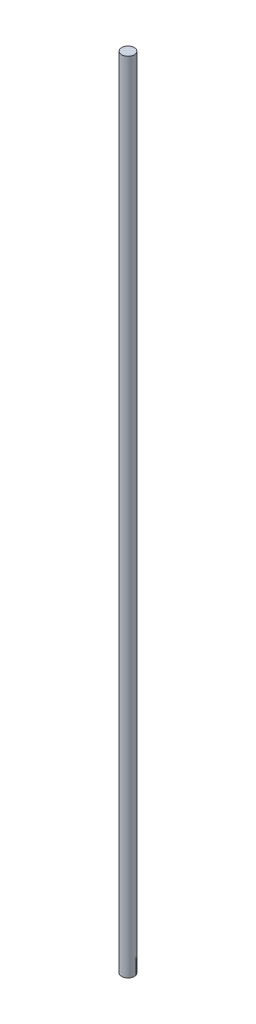
SolidWorks part; units mm, degrees
material "Pine"
ref_plane "Front" through (0, 0, 0) normal (0, 0, 1) x (1, 0, 0)
ref_plane "Top" through (0, 0, 0) normal (0, 1, 0) x (1, 0, 0)
ref_plane "Right" through (0, 0, 0) normal (1, 0, 0) x (0, 0, -1)
ref_axis "X" through (-80.9, 0, 0) along (1, 0, 0)
ref_axis "Y" through (0, -50, 0) along (0, 1, 0)
ref_axis "Z" through (0, 0, -80.9) along (0, 0, 1)
sketch "Sketch1" plane through (0, 0, 0) normal (0, 1, 0) x (1, 0, 0)
  circle A0 centre (0, 0) radius 1.5
  dimension "D1" = 3
extrude "Boss-Extrude1" add sketch "Sketch1" along normal mid plane 190.5
